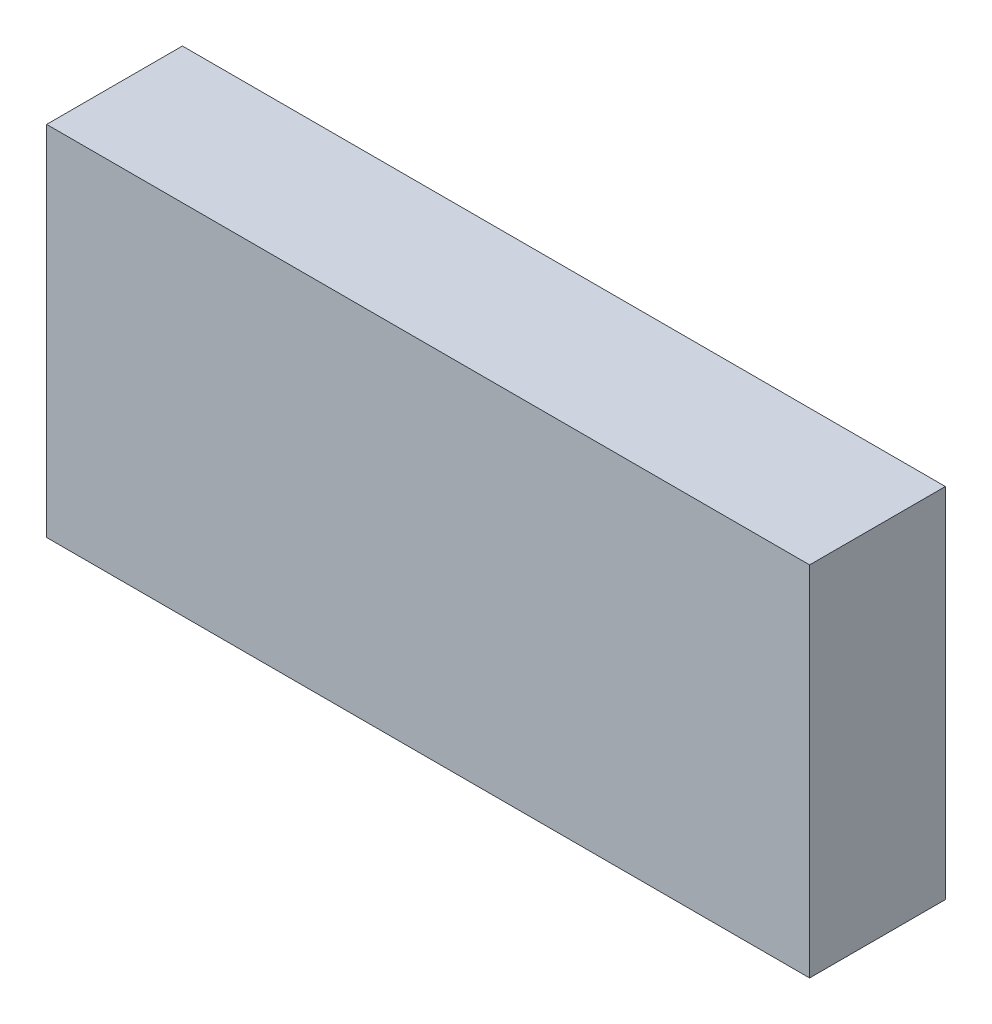
SolidWorks part; units mm, degrees
ref_plane "Front Plane" through (0, 0, 0) normal (0, 0, 1) x (1, 0, 0)
ref_plane "Top Plane" through (0, 0, 0) normal (0, 1, 0) x (1, 0, 0)
ref_plane "Right Plane" through (0, 0, 0) normal (1, 0, 0) x (0, 0, -1)
sketch "Sketch1" plane through (0, 0, 0) normal (0, 0, 1) x (1, 0, 0)
  line L1 (-22.479, -10.541) -> (22.479, -10.541)
  line L2 (-22.479, -10.541) -> (-22.479, 10.541)
  line L3 (-22.479, 10.541) -> (22.479, 10.541)
  line L4 (22.479, -10.541) -> (22.479, 10.541)
  line L5 (-22.479, -10.541) -> (22.479, 10.541) construction
  line L6 (-22.479, 10.541) -> (22.479, -10.541) construction
  point P0 (0, 0)
  dimension "D1" = 44.958
  dimension "D2" = 21.082
extrude "Boss-Extrude1" add sketch "Sketch1" along normal blind 8 contours L3 L4 L1 L2
